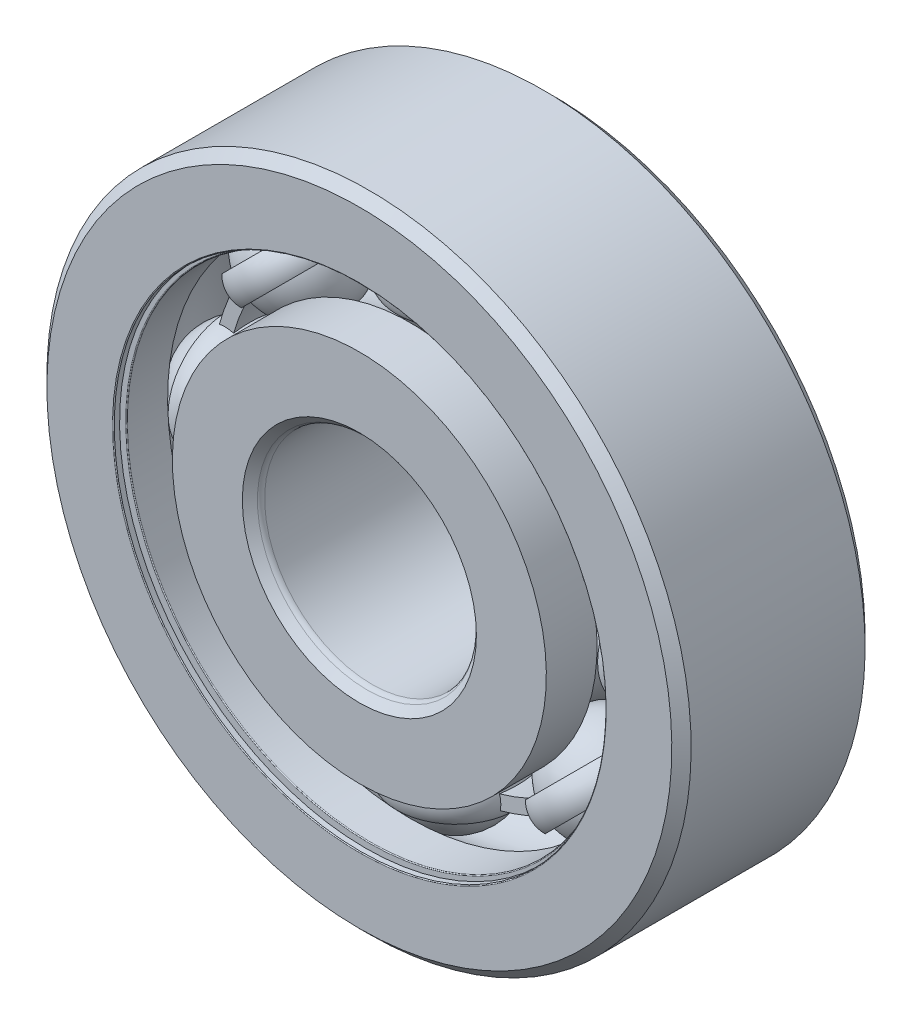
SolidWorks part; units mm, degrees
ref_plane "Front Plane" through (0, 0, 0) normal (0, 0, 1) x (1, 0, 0)
ref_plane "Top Plane" through (0, 0, 0) normal (0, 1, 0) x (1, 0, 0)
ref_plane "Right Plane" through (0, 0, 0) normal (1, 0, 0) x (0, 0, -1)
sketch "Sketch1" plane through (0, 0, 0) normal (0, 0, 1) x (1, 0, 0)
  line L0 (-15, 0) -> (15, 0) construction
  line L1 (-5, 0) -> (5, 0) construction
  circle A0 centre (0, 0) radius 5 construction
  circle A1 centre (0, 0) radius 15 construction
  point P3 (0, 0)
  point P6 (0, 0)
  point P7 (0, -5)
  point P11 (0, -15)
  point P12 (0, 5)
  point P13 (0, 15)
  dimension "OD" = 30
  dimension "ID" = 10
sketch "Sketch2" plane through (0, 0, 0) normal (1, 0, 0) x (0, 0, -1)
  line L0 (-4.5, 15) -> (4.5, 15) construction
  line L1 (0, 15) -> (0, -15) construction
  line L2 (4.05, 15) -> (-4.05, 15)
  line L3 (-4.05, 15) -> (-4.5, 14.55)
  line L4 (-4.5, 14.55) -> (-4.5, 11.2923)
  line L5 (-4.5, 11.2923) -> (-2.1375, 11.2923)
  line L6 (4.5, 11.2923) -> (2.1375, 11.2923)
  line L7 (4.5, 14.55) -> (4.5, 11.2923)
  line L8 (4.05, 15) -> (4.5, 14.55)
  line L9 (0, 15) -> (0, 10) construction
  line L10 (0, 10) -> (0, 5) construction
  line L11 (0, 15) -> (0, -15) construction
  line L12 (-4.5, 0) -> (4.5, 0) construction
  line L13 (4.5, 5) -> (-4.5, 5) construction
  line L14 (0, 12.4978) -> (0, 7.5022) construction
  line L15 (-4.5, -5) -> (4.5, -5) construction
  line L16 (-4.5, -5) -> (-4.5, 5) construction
  line L17 (4.5, 15) -> (4.5, -15) construction
  arc A0 (-2.1375, 11.2923) -> (2.1375, 11.2923) centre (0, 10) cw
  circle A1 centre (0, 10) radius 2.4978 construction
  point P14 (0, 5)
  point P17 (0, 0)
  point P21 (0, 15)
  point P29 (0, 5)
  point P30 (0, -5)
  point P35 (0, 12.4978)
  dimension "Approx. Ball Dia." = 4.9956
  dimension "Width" = 9
  dimension "D1" = 45
  dimension "D2" = 0.45
  dimension "D3" = 4.275
  dimension "D4" = 1.2923
  dimension "For Shaft Diameter" = 10
  dimension "For Housing ID" = 30
sketch "Sketch3" plane through (0, 0, 0) normal (1, 0, 0) x (0, 0, -1)
  line L0 (4.05, 15) -> (4.5, 14.55) construction
  line L1 (4.5, 14.55) -> (4.5, 11.2923) construction
  line L2 (4.5, 11.2923) -> (2.1375, 11.2923) construction
  line L3 (-4.5, 11.2923) -> (-2.1375, 11.2923) construction
  line L4 (-4.5, 14.55) -> (-4.5, 11.2923) construction
  line L5 (-4.05, 15) -> (-4.5, 14.55) construction
  line L6 (4.05, 15) -> (-4.05, 15) construction
  line L7 (4.05, 15) -> (4.5, 14.55)
  line L8 (4.5, 14.55) -> (4.5, 11.2923)
  line L9 (4.5, 11.2923) -> (2.1375, 11.2923)
  line L10 (-4.5, 11.2923) -> (-2.1375, 11.2923)
  line L11 (-4.5, 14.55) -> (-4.5, 11.2923)
  line L12 (-4.05, 15) -> (-4.5, 14.55)
  line L13 (4.05, 15) -> (-4.05, 15)
  arc A0 (2.1375, 11.2923) -> (-2.1375, 11.2923) centre (0, 10) ccw construction
  arc A1 (2.1375, 11.2923) -> (-2.1375, 11.2923) centre (0, 10) ccw
revolve "Revolve1" add sketch "Sketch3" angle 360 about L12
sketch "Sketch8" plane through (0, 0, 0) normal (1, 0, 0) x (0, 0, -1)
  line L0 (-4.5, 11.2923) -> (-2.1375, 11.2923) construction
  line L1 (-4.212, 11.2923) -> (-4.05, 11.2923)
  line L2 (-4.212, 11.2923) -> (-4.212, 12.5282) construction
  line L3 (-4.212, 12.5282) -> (-4.05, 12.5282)
  line L4 (-4.05, 11.2923) -> (-4.05, 12.5282)
  line L5 (4.5, 11.2923) -> (2.1375, 11.2923) construction
  line L6 (4.05, 11.2923) -> (4.212, 11.2923)
  line L7 (4.05, 11.2923) -> (4.05, 12.5282)
  line L8 (4.05, 12.5282) -> (4.212, 12.5282)
  line L9 (4.212, 11.2923) -> (4.212, 12.5282) construction
  line L10 (-4.05, 12.5282) -> (4.05, 12.5282) construction
  line L11 (0, 15) -> (0, -15) construction
  line L12 (-4.212, 12.5282) -> (-4.212, 13.7641) construction
  line L13 (-4.212, 13.7641) -> (-4.212, 15) construction
  line L14 (-4.5, 15) -> (4.5, 15) construction
  line L15 (-4.212, 11.2923) -> (-4.5, 11.2923)
  line L16 (-4.5, 11.2923) -> (-4.5, 11.4543)
  line L17 (-4.5, 14.55) -> (-4.5, 11.2923) construction
  line L18 (-4.5, 11.4543) -> (-4.212, 11.4543)
  line L19 (-4.212, 11.4543) -> (-4.212, 12.5282)
  line L20 (4.212, 11.2923) -> (4.5, 11.2923)
  line L21 (4.5, 11.2923) -> (4.5, 11.4543)
  line L22 (4.5, 14.55) -> (4.5, 11.2923) construction
  line L23 (4.5, 11.4543) -> (4.212, 11.4543)
  line L24 (4.212, 11.4543) -> (4.212, 12.5282)
  point P12 (0, 12.5282)
  dimension "D1" = 8.1
  dimension "D2" = 0.162
revolve "Cut-Revolve1" cut sketch "Sketch8" angle 360 about L12
sketch "Sketch4" plane through (0, 0, 0) normal (1, 0, 0) x (0, 0, -1)
  line L0 (0, 15) -> (0, -15) construction
  line L1 (0, 15) -> (0, -15) construction
  line L2 (-4.05, 5) -> (-4.5, 5.45)
  line L3 (-4.5, 5.45) -> (-4.5, 8.7077)
  line L5 (-4.5, 8.7077) -> (-2.1375, 8.7077)
  line L6 (-4.05, 5) -> (4.05, 5)
  line L8 (4.05, 5) -> (4.5, 5.45)
  line L10 (4.5, 5.45) -> (4.5, 8.7077)
  line L11 (4.5, 8.7077) -> (2.1375, 8.7077)
  line L12 (-4.5, 14.55) -> (-4.5, 11.2923) construction
  line L13 (4.05, 15) -> (4.5, 14.55) construction
  line L15 (4.5, -14.55) -> (4.5, 14.55) construction
  line L16 (4.05, 15) -> (4.05, -15) construction
  arc A1 (2.1375, 8.7077) -> (-2.1375, 8.7077) centre (0, 10) cw
  circle A2 centre (0, 10) radius 2.4978 construction
  point P1 (0, 5)
revolve "Revolve2" add sketch "Sketch4" angle 360 about L12
sketch "Sketch5" plane through (0, 0, 0) normal (1, 0, 0) x (0, 0, -1)
  line L0 (-2.4978, 10) -> (2.4978, 10)
  arc A2 (-2.4978, 10) -> (2.4978, 10) centre (0, 10) cw
  arc A3 (2.1375, 11.2923) -> (-2.1375, 11.2923) centre (0, 10) ccw construction
revolve "Revolve3" add sketch "Sketch5" angle 360 about L0
sketch "Sketch6" plane through (0, 0, 0) normal (1, 0, 0) x (0, 0, -1)
  line L0 (-2.1375, 11.2923) -> (-2.1375, 10.6462) construction
  line L1 (-2.1375, 10.6462) -> (-2.1375, 10) construction
  line L2 (-2.1375, 10) -> (-2.1375, 9.3538) construction
  line L3 (-2.1375, 9.3538) -> (-2.1375, 8.7077) construction
  line L4 (-4.5, 10.6462) -> (-4.1521, 10.6462) construction
  line L5 (-2.1375, 10.6462) -> (-2.1375, 9.3538) construction
  line L7 (-4.1521, 10.6462) -> (-3.8043, 10.6462) construction
  line L8 (-3.8043, 10.6462) -> (-3.4564, 10.6462) construction
  line L10 (0, 15) -> (0, -15) construction
  line L11 (0, 15) -> (0, -15) construction
  line L12 (-4.5, 11.2923) -> (-4.5, 10.6462) construction
  line L13 (-2.7606, 10.6462) -> (-2.4128, 10.6462) construction
  line L14 (-4.5, 14.55) -> (-4.5, -14.55) construction
  line L15 (-4.5, 10.6462) -> (-4.5, 10) construction
  line L16 (-4.5, 10) -> (-4.5, 9.3538) construction
  line L17 (-4.5, 9.3538) -> (-4.5, 8.7077) construction
  line L18 (-3.4564, 10.6462) -> (-3.1085, 10.6462) construction
  line L19 (-3.1085, 10.6462) -> (-2.7606, 10.6462) construction
  line L20 (-2.4128, 10.6462) -> (-2.7606, 10.6462)
  line L21 (-4.5, 9.3538) -> (-4.1521, 9.3538) construction
  line L22 (-4.1521, 9.3538) -> (-3.8043, 9.3538) construction
  line L23 (-3.8043, 9.3538) -> (-3.4564, 9.3538) construction
  line L24 (-3.4564, 9.3538) -> (-3.1085, 9.3538) construction
  line L25 (-3.1085, 9.3538) -> (-2.7606, 9.3538) construction
  line L26 (-2.7606, 9.3538) -> (-2.4128, 9.3538) construction
  line L27 (-2.4128, 9.3538) -> (-2.7606, 9.3538)
  line L28 (-3.1085, 10.6462) -> (-3.1085, 9.3538) construction
  line L30 (-2.9346, 10.6462) -> (-2.9346, 9.3538) construction
  circle A0 centre (0, 10) radius 2.4978 construction
  arc A2 (-2.7606, 9.3538) -> (-2.7606, 10.6462) centre (-1.6474, 10) cw
  arc A3 (-2.4128, 10.6462) -> (-2.4128, 9.3538) centre (0, 10) ccw
revolve "Revolve4" add sketch "Sketch6" angle 360 about L11
sketch "Sketch7" plane through (0, 0, 0) normal (0, 0, 1) x (1, 0, 0)
  line L0 (-2.4978, 10) -> (2.4978, 10) construction
  line L1 (0, 7.5022) -> (0, 12.4978) construction
  line L2 (0, 0) -> (3.8268, 9.2388) construction
  line L8 (0, 15) -> (0, -15) construction
  line L9 (7.0711, 7.0711) -> (7.528, 7.528)
  line L10 (0, 15) -> (0, -15) construction
  line L11 (0, 10.6462) -> (0, 10)
  arc A1 (7.0711, 7.0711) -> (0, 10) centre (0, 0) ccw
  arc A2 (7.528, 7.528) -> (0, 10.6462) centre (0, 0) ccw
  dimension "D1" = 45
  dimension "D2" = 4.9956
extrude "Boss-Extrude1" add sketch "Sketch7" along normal mid plane 1.5
pattern_circular "CirPattern1" count 8 over 360 about axis through (0, 0, 4.5) along (0, 0, -1) of bodies 104 134
pattern_circular "CirPattern2" count 8 over 360 about axis through (0, 0, 4.5) along (0, 0, -1) of "Revolve4", "Boss-Extrude1" reverse direction yes
fillet "Fillet1" radius 0.0405 4 edges at (0, -11.2923, -4.05) (0, -11.4543, -4.5) (0, -11.2923, 4.05) (0, -11.4543, 4.5)
fillet "Fillet2" radius 0.3375 2 edges at (0, -5, -4.05) (0, -5, 4.05)
ref_plane "Plane1" through (3.8268, 9.2388, 0) normal (0.3827, 0.9239, 0) x (0.9239, -0.3827, 0)
sketch "Sketch9" plane through (3.8268, 9.2388, 0) normal (0.3827, 0.9239, 0) x (0.9239, -0.3827, 0)
  line L0 (-1.5192, -0.75) -> (-1.5192, -2.25)
  line L1 (-1.5192, -2.25) -> (-0.659, -2.25)
  line L2 (-0.659, -2.25) -> (0, -1.6971)
  line L3 (0, -1.6971) -> (0.659, -2.25)
  line L4 (0.659, -2.25) -> (1.5192, -2.25)
  line L5 (1.5192, -2.25) -> (1.5192, -0.75)
  line L6 (1.5192, -0.75) -> (-1.5192, -0.75)
  line L7 (0, -0.75) -> (0, 0) construction
  line L8 (-1.5192, -0.75) -> (-1.5192, 0) construction
  dimension "D1" = 1.5
  dimension "D2" = 0.75
  dimension "D3" = 40
extrude "Boss-Extrude2" [suppressed] add sketch "Sketch9" along normal blind 2.1856 draft 15 and the other way blind 2.1856 draft 10 separate body draft outward yes other way draft outward yes
fillet "Fillet3" [suppressed] radius 0.45
mirror "Mirror1" [suppressed] about plane through (0, 0, 0) normal (0, 0, 1) of bodies 149
pattern_circular "CirPattern3" [suppressed] count 8 over 360 about axis through (0, 0, 4.5) along (0, 0, -1) of bodies 158 149
equation "\"D2@Sketch2\" = \"Width@Sketch2\" * .05"
equation "\"D3@Sketch2\"=\"Width@Sketch2\" * .475"
equation "\"D4@Sketch2\" =  (  (  ( \"OD@Sketch1\" - \"Width@Sketch2\" )  / 2 )  / 3.25 )  / 2.5"
equation "\"D1@Boss-Extrude1\" = \"Width@Sketch2\" / 6"
equation "\"D1@Sketch8\"=\"Width@Sketch2\"*.9"
equation "\"D2@Sketch8\"=\"D1@Sketch8\"*.02"
equation "\"D1@Fillet1\" = \"D2@Sketch8\" * .25"
equation "\"D1@Fillet2\" = \"D2@Sketch2\" * .75"
equation "\"Approx No of Balls@CirPattern1\" = ( pi * \"OD@Sketch1\" ) * .4 / \"Approx. Ball Dia.@Sketch2\""
equation "\"D1@Sketch7\" = 360 / \"Approx No of Balls@CirPattern1\""
equation "\"D1@CirPattern2\" = \"Approx No of Balls@CirPattern1\""
equation "\"D2@Sketch7\"=\"Approx. Ball Dia.@Sketch2\""
equation "\"D2@Sketch9\" = \"D1@Boss-Extrude1\" * .5"
equation "\"D1@Sketch9\"=\"D2@Sketch9\"*2"
equation "\"D1@Boss-Extrude2\"=\"Approx. Ball Dia.@Sketch2\"*.4375"
equation "\"D2@Boss-Extrude2\"=\"D1@Boss-Extrude2\""
equation "\"D1@CirPattern3\" = \"Approx No of Balls@CirPattern1\""
equation "\"D1@Fillet3\"=\"D1@Sketch9\" * .3"
